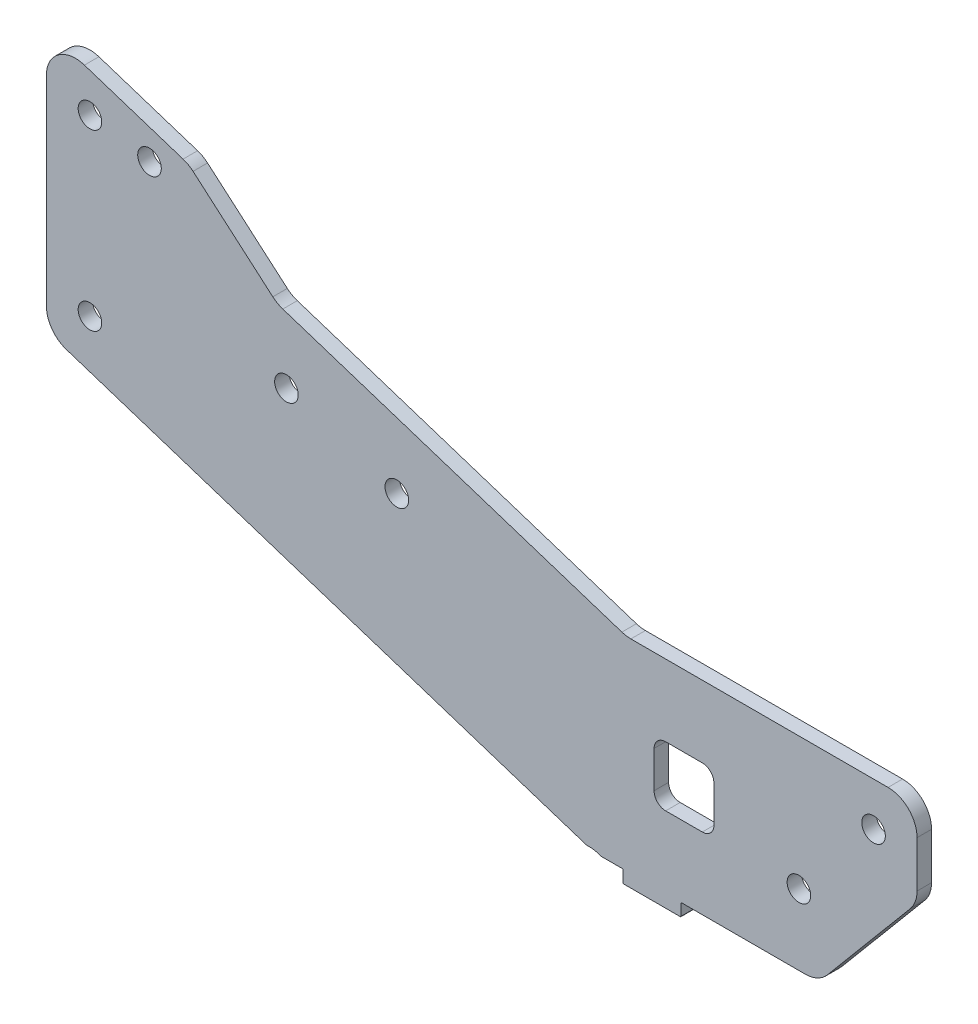
SolidWorks part; units mm, degrees
material "PL,44W"
ref_plane "Front" through (0, 0, 0) normal (0, 0, 1) x (1, 0, 0)
ref_plane "Top" through (0, 0, 0) normal (0, 1, 0) x (1, 0, 0)
ref_plane "Right" through (0, 0, 0) normal (1, 0, 0) x (0, 0, -1)
sketch "Sketch2" plane through (0, 0, 0) normal (0, 0, 1) x (1, 0, 0)
  line L0 (0, 9.2261) -> (0, 96.8181)
  line L2 (255.7538, 11.0039) -> (368.3, 11.0039)
  line L3 (381, -1.6961) -> (381, -21.9253)
  line L4 (378.0288, -30.0887) -> (341.7203, -73.3595)
  line L5 (331.9915, -77.8961) -> (239.6567, -77.8961)
  line L6 (239.6567, -77.8961) -> (8.7743, -2.8519)
  line L7 (251.8281, 11.6259) -> (103.4368, 59.8578)
  line L8 (99.0706, 62.3164) -> (64.1656, 92.4047)
  line L9 (59.7993, 94.8633) -> (16.6257, 108.8961)
  arc A1 (103.4368, 59.8578) -> (99.0706, 62.3164) centre (107.3626, 71.9358) cw
  arc A2 (64.1656, 92.4047) -> (59.7993, 94.8633) centre (55.8736, 82.7853) ccw
  arc A3 (0, 96.8181) -> (16.6257, 108.8961) centre (12.7, 96.8181) cw
  arc A4 (0, 9.2261) -> (8.7743, -2.8519) centre (12.7, 9.2261) ccw
  arc A5 (341.7203, -73.3595) -> (331.9915, -77.8961) centre (331.9915, -65.1961) cw
  arc A6 (381, -21.9253) -> (378.0288, -30.0887) centre (368.3, -21.9253) cw
  arc A7 (368.3, 11.0039) -> (381, -1.6961) centre (368.3, -1.6961) cw
  arc A8 (251.8281, 11.6259) -> (255.7538, 11.0039) centre (255.7538, 23.7039) ccw
  point P16 (0, 114.3)
  point P19 (0, 0)
  dimension "D3" = 12.7
  dimension "D4" = 12.7
  dimension "D5" = 12.7
  dimension "D1" = 114.3
  dimension "D2" = 88.9
  dimension "D6" = 381
  dimension "D7" = 92.3348
  dimension "D8" = 88.9
  dimension "D9" = 161.994
  dimension "D10" = 157.244
  dimension "D12" = 112.5462
  dimension "D13" = 43.1736
  dimension "D14" = 130
base flange "Base-Flange1" sketch "Sketch2" thickness 6.35 reverse thickness direction no parameters "D1"=7.9502
sketch "Sketch7" plane through (0, 0, 0) normal (0, 0, 1) x (1, 0, 0)
  line L0 (252.3567, -77.8961) -> (252.3567, -83.4524)
  line L1 (239.6567, -77.8961) -> (331.9915, -77.8961) construction
  line L2 (252.3567, -83.4524) -> (277.7567, -83.4524)
  line L3 (277.7567, -83.4524) -> (277.7567, -77.8961)
  line L4 (277.7567, -77.8961) -> (252.3567, -77.8961)
  dimension "D1" = 25.4
  dimension "D2" = 12.7
  dimension "D3" = 5.5562
base flange "Tab1" sketch "Sketch7" thickness 6.35 reverse thickness direction no parameters "D1"=7.9502
sketch "Sketch10" plane through (0, 0, 0) normal (0, 0, 1) x (1, 0, 0)
  line L0 (381, -21.9253) -> (381, -1.6961) construction
  line L1 (368.3, 11.0039) -> (255.7538, 11.0039) construction
  line L2 (361.95, -8.0461) -> (329.2964, -46.9612) construction
  line L3 (0, 96.8181) -> (0, 9.2261) construction
  line L4 (45.1119, 86.5267) -> (19.05, 14.9221) construction
  line L5 (19.05, 91.1221) -> (19.05, 14.9221) construction
  line L6 (251.8281, 11.6259) -> (103.4368, 59.8578) construction
  line L7 (105.0232, 30.6251) -> (153.3353, 14.9221) construction
  circle A0 centre (361.95, -8.0461) radius 5.1594
  circle A1 centre (329.2964, -46.9612) radius 5.1594
  circle A2 centre (19.05, 91.1221) radius 5.1594
  circle A3 centre (19.05, 14.9221) radius 5.1594
  circle A4 centre (45.1119, 86.5267) radius 5.1594
  circle A5 centre (153.3353, 14.9221) radius 5.1594
  circle A6 centre (105.0232, 30.6251) radius 5.1594
  point P17 (0, 53.0221)
  dimension "D1" = 10.3187
  dimension "D2" = 19.05
  dimension "D3" = 19.05
  dimension "D4" = 50.8
  dimension "D5" = 40
  dimension "D6" = 19.05
  dimension "D7" = 38.1
  dimension "D8" = 38.1
  dimension "D9" = 76.2
  dimension "D10" = 20
  dimension "D11" = 27.3107
  dimension "D12" = 50.8
  dimension "D13" = 153.3353
extrude "Cut-Extrude1" cut sketch "Sketch10" against normal through all normal cut yes
sketch "Sketch11" plane through (0, 0, 0) normal (0, 0, 1) x (1, 0, 0)
  line L0 (381, -77.8961) -> (381, 11.0039) construction
  line L1 (270.9862, -20.3493) -> (287.02, -20.3493)
  line L2 (265.9063, -25.4293) -> (265.9063, -41.463)
  line L3 (270.9862, -46.543) -> (287.02, -46.543)
  line L4 (292.1, -25.4293) -> (292.1, -41.463)
  line L7 (381, -21.9253) -> (381, -1.6961) construction
  line L8 (368.3, 11.0039) -> (255.7538, 11.0039) construction
  line L9 (277.7567, -77.8961) -> (331.9915, -77.8961) construction
  arc A0 (287.02, -20.3493) -> (292.1, -25.4293) centre (287.02, -25.4293) cw
  arc A1 (287.02, -46.543) -> (292.1, -41.463) centre (287.02, -41.463) ccw
  arc A2 (265.9063, -41.463) -> (270.9862, -46.543) centre (270.9862, -41.463) ccw
  arc A3 (270.9862, -20.3493) -> (265.9063, -25.4293) centre (270.9862, -25.4293) ccw
  point P6 (292.1, -20.3493)
  point P9 (292.1, -46.543)
  point P20 (292.1, -33.4461)
  point P25 (381, -33.4461)
  dimension "D2" = 5.08
  dimension "D1" = 26.1937
  dimension "D3" = 88.9
  dimension "D4" = 381
extrude "Cut-Extrude2" cut sketch "Sketch11" against normal through all normal cut yes
sketch "Sketch12" plane through (0, 0, 0) normal (0, 0, 1) x (1, 0, 0)
  line L0 (252.3567, -77.8961) -> (252.3567, -83.4524) construction
  line L3 (239.6567, -77.8961) -> (252.3567, -77.8961) construction
  circle A0 centre (237.5512, -89.5278) radius 12.7
  dimension "D1" = 25.4
  dimension "D2" = 14.8055
  dimension "D3" = 11.6317
extrude "Cut-Extrude4" cut sketch "Sketch12" against normal through all normal cut yes
fillet "Fillet1" radius 2.54 2 edges at (242.6496, -77.8961, -3.175) (236.5032, -76.8711, -3.175)
fillet "Fillet2" radius 0.3969 4 edges at (252.3567, -77.8961, -3.175) (252.3567, -83.4524, -3.175) (277.7567, -83.4524, -3.175) (277.7567, -77.8961, -3.175)
sketch "Bend-Lines1" [suppressed] plane through (0, 0, 0) normal (0, 1, 0) x (1, 0, 0)
sketch "Bounding-Box1" [suppressed] plane through (0, 0, 0) normal (0, 1, 0) x (1, 0, 0)
sheet metal parameters "Sheet-Metal28" thickness 6.35 parameters "D1"=5.9436
flat pattern "Flat-Pattern28" [suppressed]
sketch "Bend-Lines2" plane through (0, 0, 0) normal (0, 1, 0) x (1, 0, 0)
sketch3d "Bounding-Box2" [suppressed]
  line L0 (-6.0529, 108.0949, 0) -> (458.4149, -75.424, 0) construction
  line L1 (-55.0513, -15.9151, 0) -> (409.4165, -199.4339, 0) construction
  line L2 (-6.0529, 108.0949, 0) -> (-55.0513, -15.9151, 0) construction
  line L3 (458.4149, -75.424, 0) -> (409.4165, -199.4339, 0) construction
sheet metal parameters "Sheet-Metal29" thickness 6.35 parameters "D1"=5.9436
flat pattern "Flat-Pattern29"
sketch "Bend-Lines3" plane through (0, 0, 0) normal (0, 1, 0) x (1, 0, 0)
sketch3d "Bounding-Box3" [suppressed]
  line L0 (-6.0996, 108.2313, 0) -> (458.4118, -72.9271, 0) construction
  line L1 (-54.5446, -15.9873, 0) -> (409.9668, -197.1457, 0) construction
  line L2 (-6.0996, 108.2313, 0) -> (-54.5446, -15.9873, 0) construction
  line L3 (458.4118, -72.9271, 0) -> (409.9668, -197.1457, 0) construction
sheet metal parameters "Sheet-Metal30" thickness 6.35 parameters "D1"=5.9436
flat pattern "Flat-Pattern29"
sketch "Bend-Lines3" plane through (0, 0, 0) normal (0, 1, 0) x (1, 0, 0)
sketch3d "Bounding-Box3" [suppressed]
  line L0 (-8.7254, 103.2906, 0) -> (452.8389, -28.4889, 0) construction
  line L1 (-42.5333, -15.1233, 0) -> (419.0309, -146.9028, 0) construction
  line L2 (-8.7254, 103.2906, 0) -> (-42.5333, -15.1233, 0) construction
  line L3 (452.8389, -28.4889, 0) -> (419.0309, -146.9028, 0) construction
sheet metal parameters "Sheet-Metal31" thickness 6.35 parameters "D1"=5.9436
flat pattern "Flat-Pattern29"
sketch "Bend-Lines3" plane through (0, 0, 0) normal (0, 1, 0) x (1, 0, 0)
sketch3d "Bounding-Box3" [suppressed]
  line L0 (-8.7254, 103.2906, 0) -> (452.8389, -28.4889, 0) construction
  line L1 (-42.5333, -15.1233, 0) -> (419.0309, -146.9028, 0) construction
  line L2 (-8.7254, 103.2906, 0) -> (-42.5333, -15.1233, 0) construction
  line L3 (452.8389, -28.4889, 0) -> (419.0309, -146.9028, 0) construction
sheet metal parameters "Sheet-Metal33" thickness 6.35 parameters "D1"=5.9436
flat pattern "Flat-Pattern29"
sketch "Bend-Lines3" plane through (0, 0, 0) normal (0, 1, 0) x (1, 0, 0)
sketch3d "Bounding-Box3" [suppressed]
  line L0 (-8.8484, 103.2216, 0) -> (376.4344, -3.5158, 0) construction
  line L1 (-41.5138, -14.6887, 0) -> (343.7689, -121.4261, 0) construction
  line L2 (-8.8484, 103.2216, 0) -> (-41.5138, -14.6887, 0) construction
  line L3 (376.4344, -3.5158, 0) -> (343.7689, -121.4261, 0) construction
equation "\"Total Cutting Length\"= \"Cutting Length-Outer\" + \"Cutting Length-Inner\""
equation "\"Amount in ft^2\"= \"Bounding Box Area-Blank\" / 144"
